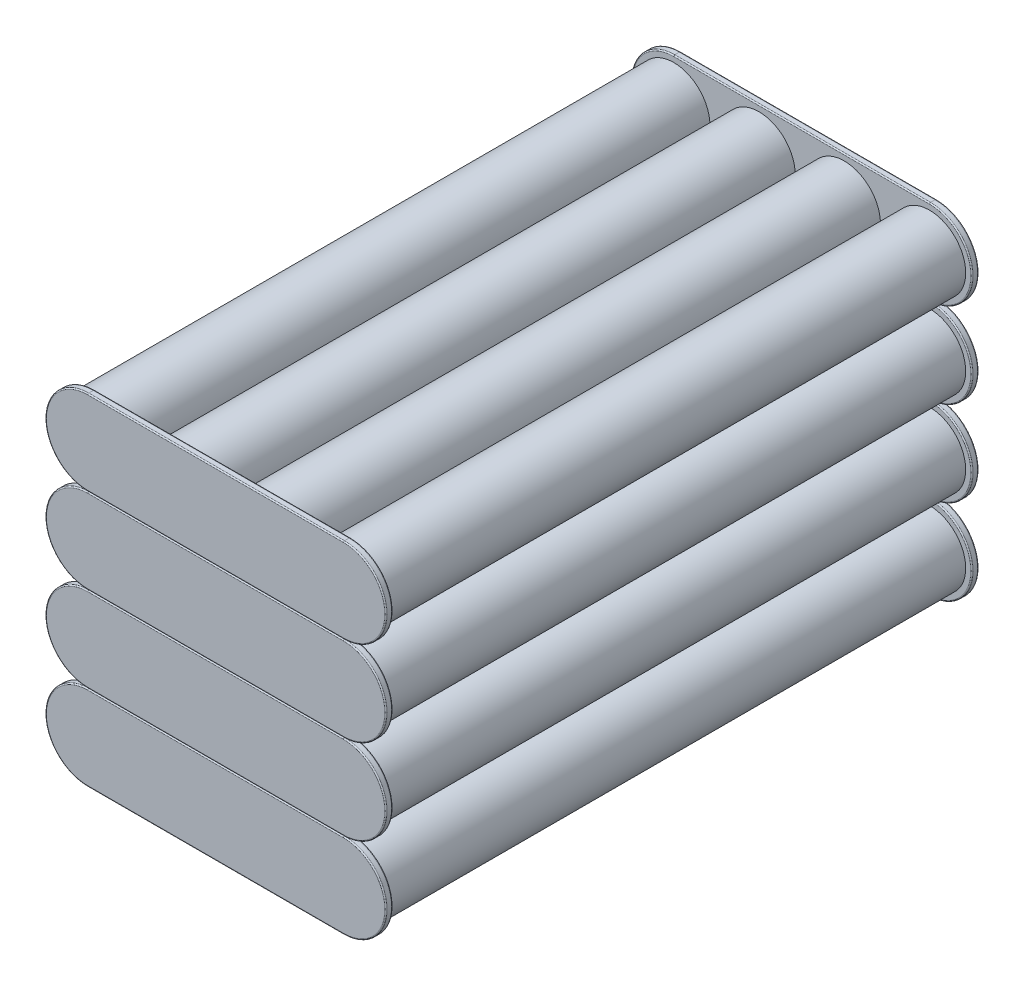
SolidWorks part; units mm, degrees
ref_plane "Front Plane" through (0, 0, 0) normal (0, 0, 1) x (1, 0, 0)
ref_plane "Top Plane" through (0, 0, 0) normal (0, 1, 0) x (1, 0, 0)
ref_plane "Right Plane" through (0, 0, 0) normal (1, 0, 0) x (0, 0, -1)
sketch "Sketch1" plane through (0, 0, 0) normal (0, 0, 1) x (1, 0, 0)
  circle A3 centre (101.4639, 0) radius 80.6924
  circle A16 centre (291.4639, 0) radius 80.6924
  circle A17 centre (481.4639, 0) radius 80.6924
  circle A18 centre (671.4639, 0) radius 80.6924
  circle A19 centre (291.4639, 190) radius 80.6924
  circle A20 centre (481.4639, 190) radius 80.6924
  circle A21 centre (671.4639, 190) radius 80.6924
  circle A22 centre (291.4639, 380) radius 80.6924
  circle A23 centre (481.4639, 380) radius 80.6924
  circle A24 centre (671.4639, 380) radius 80.6924
  circle A25 centre (291.4639, 570) radius 80.6924
  circle A26 centre (481.4639, 570) radius 80.6924
  circle A27 centre (671.4639, 570) radius 80.6924
  circle A43 centre (101.4639, 190) radius 80.6924
  circle A44 centre (101.4639, 380) radius 80.6924
  circle A45 centre (101.4639, 570) radius 80.6924
  dimension "D1" = 4
extrude "Boss-Extrude1" add sketch "Sketch1" along normal blind 1291.079
sketch "Sketch3" plane through (0, 0, 0) normal (0, 0, 1) x (1, 0, 0)
  line L0 (101.4639, 0) -> (671.4639, 0) construction
  line L1 (101.4639, 94.5614) -> (671.4639, 94.5614)
  line L2 (101.4639, -94.5614) -> (671.4639, -94.5614)
  arc A0 (101.4639, 94.5614) -> (101.4639, -94.5614) centre (101.4639, 0) ccw
  arc A1 (671.4639, -94.5614) -> (671.4639, 94.5614) centre (671.4639, 0) ccw
  point P4 (386.4639, 0)
extrude "Boss-Extrude4" add sketch "Sketch3" against normal blind 15
fillet "Fillet2" radius 2.5 8 edges at (386.4639, -94.5614, 0) (386.4639, -94.5614, -15) (766.0252, 0, 0) (766.0252, 0, -15) (6.9025, 0, 0) (6.9025, 0, -15) (386.4639, 94.5614, 0) (386.4639, 94.5614, -15)
pattern_linear "LPattern1" count 4 spacing 190 along (0, 1, 0) of "Boss-Extrude4"
fillet "Fillet3" radius 2.5 8 edges at (766.0252, 190, 0) (386.4639, 95.4386, 0) (6.9025, 190, 0) (766.0252, 190, -15) (386.4639, 95.4386, -15) (6.9025, 190, -15) (386.4639, 284.5614, 0) (386.4639, 284.5614, -15)
fillet "Fillet4" radius 2.5 8 edges at (766.0252, 380, 0) (386.4639, 285.4386, 0) (6.9025, 380, 0) (766.0252, 380, -15) (386.4639, 285.4386, -15) (6.9025, 380, -15) (386.4639, 474.5614, 0) (386.4639, 474.5614, -15)
fillet "Fillet5" radius 2.5 8 edges at (766.0252, 570, 0) (386.4639, 475.4386, 0) (6.9025, 570, 0) (766.0252, 570, -15) (386.4639, 475.4386, -15) (6.9025, 570, -15) (386.4639, 664.5614, 0) (386.4639, 664.5614, -15)
sketch "Sketch7" plane through (0, 0, 1291.079) normal (0, 0, 1) x (1, 0, 0)
  line L0 (671.4639, 0) -> (101.4639, 0) construction
  line L1 (671.4639, -94.5614) -> (101.4639, -94.5614)
  line L2 (671.4639, 94.5614) -> (101.4639, 94.5614)
  arc A0 (671.4639, -94.5614) -> (671.4639, 94.5614) centre (671.4639, 0) ccw
  arc A1 (101.4639, 94.5614) -> (101.4639, -94.5614) centre (101.4639, 0) ccw
  point P4 (386.4639, 0)
extrude "Boss-Extrude5" add sketch "Sketch7" along normal blind 15
pattern_linear "LPattern2" count 4 spacing 190 along (0, 1, 0) of "Boss-Extrude5"
fillet "Fillet6" radius 2.5 8 edges at (766.0252, 570, 1291.079) (386.4639, 475.4386, 1291.079) (6.9025, 570, 1291.079) (766.0252, 570, 1306.079) (386.4639, 475.4386, 1306.079) (6.9025, 570, 1306.079) (386.4639, 664.5614, 1291.079) (386.4639, 664.5614, 1306.079)
fillet "Fillet7" radius 2.5 8 edges at (766.0252, 380, 1306.079) (386.4639, 285.4386, 1306.079) (6.9025, 380, 1306.079) (766.0252, 380, 1291.079) (386.4639, 285.4386, 1291.079) (6.9025, 380, 1291.079) (386.4639, 474.5614, 1306.079) (386.4639, 474.5614, 1291.079)
fillet "Fillet8" radius 2.5 8 edges at (766.0252, 190, 1291.079) (386.4639, 95.4386, 1291.079) (6.9025, 190, 1291.079) (766.0252, 190, 1306.079) (386.4639, 95.4386, 1306.079) (6.9025, 190, 1306.079) (386.4639, 284.5614, 1291.079) (386.4639, 284.5614, 1306.079)
fillet "Fillet9" radius 2.5 8 edges at (6.9025, 0, 1291.079) (386.4639, 94.5614, 1291.079) (766.0252, 0, 1291.079) (6.9025, 0, 1306.079) (386.4639, 94.5614, 1306.079) (766.0252, 0, 1306.079) (386.4639, -94.5614, 1291.079) (386.4639, -94.5614, 1306.079)
